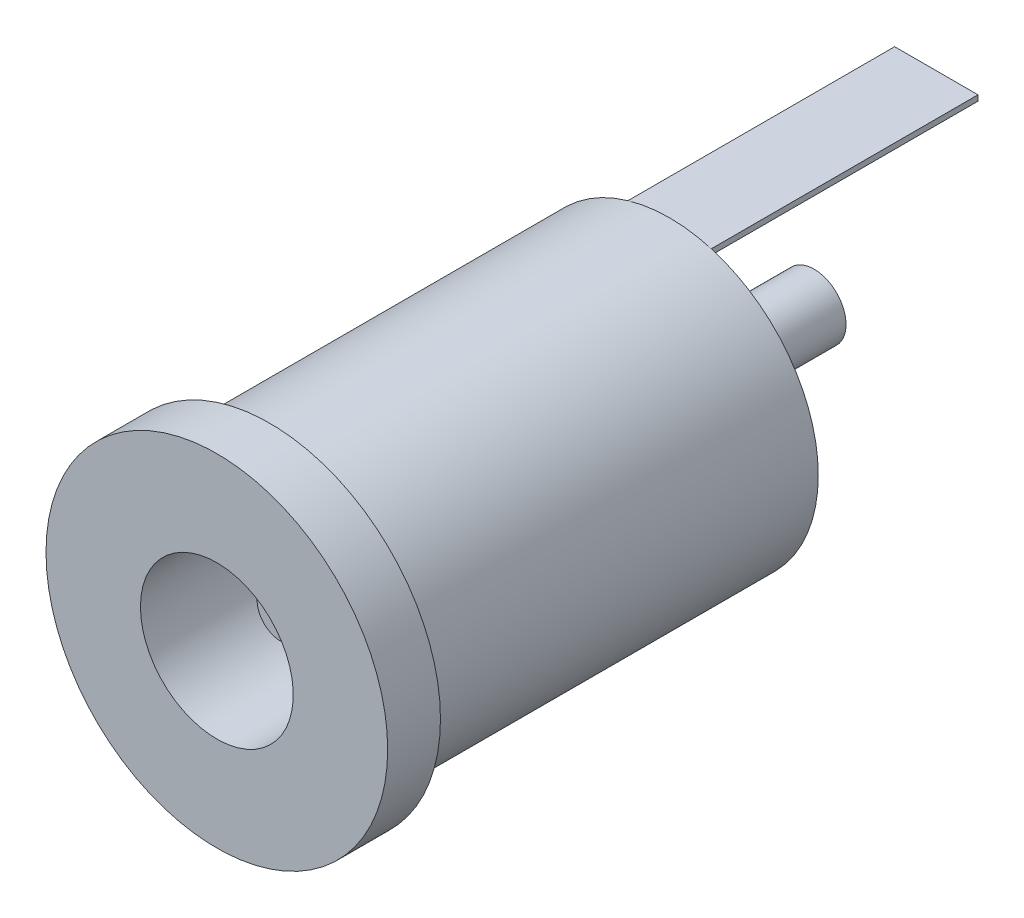
SolidWorks part; units mm, degrees
ref_plane "Front Plane" through (0, 0, 0) normal (0, 0, 1) x (1, 0, 0)
ref_plane "Top Plane" through (0, 0, 0) normal (0, 1, 0) x (1, 0, 0)
ref_plane "Right Plane" through (0, 0, 0) normal (1, 0, 0) x (0, 0, -1)
sketch "Sketch1" plane through (0, 0, 0) normal (0, 0, 1) x (1, 0, 0)
  circle A0 centre (0, 0) radius 6.15
  circle A1 centre (0, 0) radius 2.75
  circle A2 centre (0, 0) radius 5.35
  dimension "D1" = 12.3
  dimension "D2" = 5.5
  dimension "D3" = 10.7
extrude "Boss-Extrude1" add sketch "Sketch1" along normal blind 1.9 contours A0 A2 | A2 A1 region at (-5.9761, 0, 0) region at (-5.1987, 0, 0)
extrude "Boss-Extrude2" add sketch "Sketch1<3>" against normal blind 14.4 contours A2 A1 region at (-5.1987, 0, 0)
sketch "Sketch1<3>" plane through (0, 0, 0) normal (0, 0, 1) x (1, 0, 0) same geometry as "Sketch1"
ref_plane "Plane1" through (0, 0, -14.4) normal (0, 0, -1) x (-1, 0, 0)
sketch "Sketch2" plane through (0, 0, -14.4) normal (0, 0, -1) x (-1, 0, 0)
  line L0 (0, 0) -> (0, 5.35) construction
  line L2 (-1.5, 5.1354) -> (1.5, 5.1354)
  line L3 (-1.5, 5.1354) -> (-1.5, 4.9354)
  line L4 (-1.5, 4.9354) -> (1.5, 4.9354)
  line L5 (1.5, 5.1354) -> (1.5, 4.9354)
  line L6 (-1.5, 5.1354) -> (1.5, 4.9354) construction
  line L7 (-1.5, 4.9354) -> (1.5, 5.1354) construction
  circle A0 centre (0, 0) radius 0.85
  circle A1 centre (0, 0) radius 2.75 construction
  circle A2 centre (0, 0) radius 2.75
  circle A3 centre (0, 0) radius 1.15
  circle A4 centre (0, 0) radius 5.35 construction
  circle A5 centre (0, 0) radius 1.9
  point P7 (0, 5.0354)
  dimension "D1" = 1.7
  dimension "D2" = 2.3
  dimension "D5" = 3.8
  dimension "D3" = 3
  dimension "D4" = 0.2
extrude "Boss-Extrude3" add sketch "Sketch2" against normal blind 3 contours A2 A5 | A5 A3 | A3 A0 | A0 region at (0, 0, -14.4) region at (2.6722, 0, -14.4) region at (1.1175, 0, -14.4) region at (1.8463, 0, -14.4)
extrude "Boss-Extrude4" add sketch "Sketch2<3>" along normal blind 0.8 contours A3 A0 | A0 | A5 A3 region at (0, 0, -14.4) region at (1.1175, 0, -14.4) region at (1.8463, 0, -14.4)
sketch "Sketch2<3>" plane through (0, 0, -14.4) normal (0, 0, -1) x (-1, 0, 0) same geometry as "Sketch2"
extrude "Boss-Extrude5" add sketch "Sketch2<5>" against normal blind 14 contours A0 region at (0, 0, -14.4)
sketch "Sketch2<5>" plane through (0, 0, -14.4) normal (0, 0, -1) x (-1, 0, 0) same geometry as "Sketch2"
extrude "Boss-Extrude6" add sketch "Sketch2<6>" along normal blind 5.2 contours A3 A0 | A0 region at (0, 0, -14.4) region at (1.1175, 0, -14.4)
sketch "Sketch2<6>" plane through (0, 0, -14.4) normal (0, 0, -1) x (-1, 0, 0) same geometry as "Sketch2"
extrude "Boss-Extrude7" add sketch "Sketch2<7>" along normal blind 9.6 contours L2 L5 L4 L3
sketch "Sketch2<7>" plane through (0, 0, -14.4) normal (0, 0, -1) x (-1, 0, 0) same geometry as "Sketch2"
